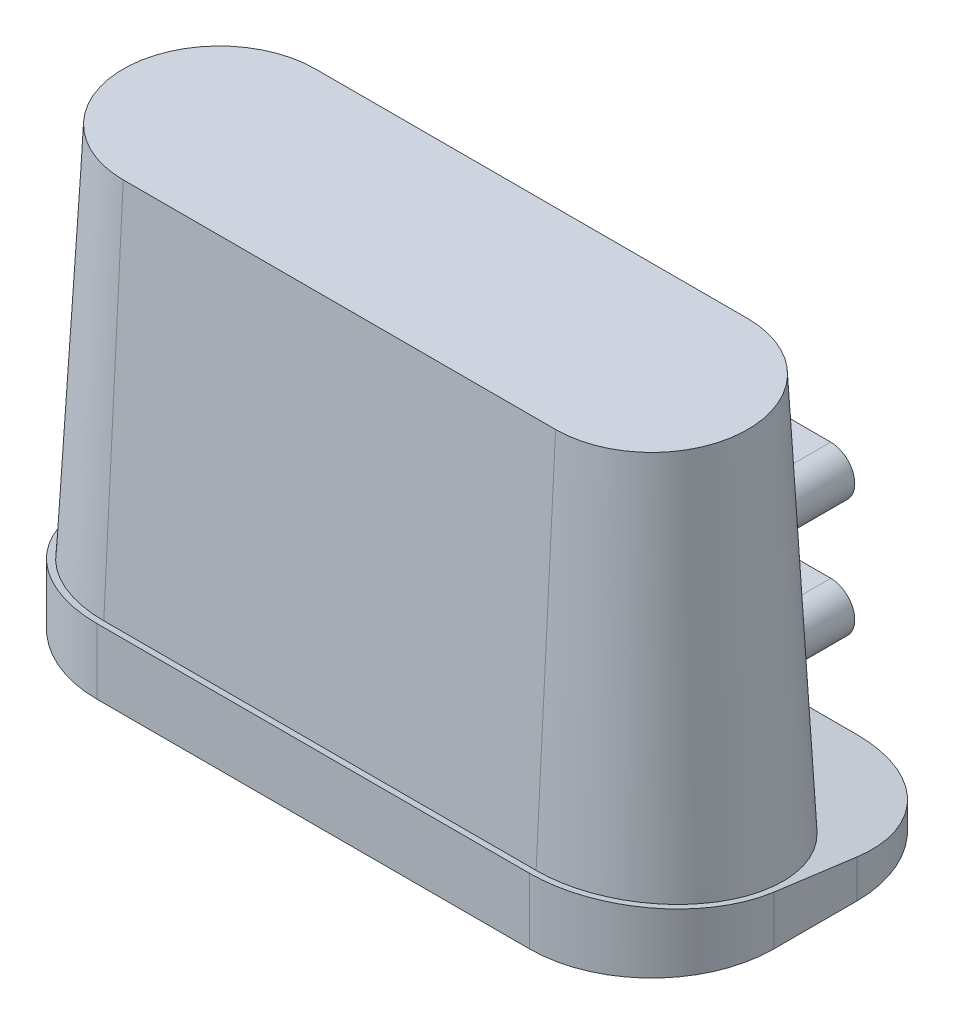
SolidWorks part; units mm, degrees
ref_plane "정면" through (0, 0, 0) normal (0, 0, 1) x (1, 0, 0)
ref_plane "윗면" through (0, 0, 0) normal (0, 1, 0) x (1, 0, 0)
ref_plane "우측면" through (0, 0, 0) normal (1, 0, 0) x (0, 0, -1)
sketch "스케치2" plane through (0, 0, 0) normal (0, 1, 0) x (1, 0, 0)
  line L1 (-77.5, -37.5) -> (77.5, -37.5)
  line L2 (-77.5, -37.5) -> (-77.5, 37.5)
  line L3 (-77.5, 37.5) -> (77.5, 37.5)
  line L4 (77.5, -37.5) -> (77.5, 37.5)
  line L5 (-77.5, -37.5) -> (77.5, 37.5) construction
  line L6 (-77.5, 37.5) -> (77.5, -37.5) construction
  point P0 (0, 0)
  dimension "D1" = 155
  dimension "D2" = 75
extrude "보스-돌출1" add sketch "스케치2" along normal blind 15
sketch "스케치3" plane through (77.5, 0, 0) normal (1, 0, 0) x (0, 0, -1)
  line L1 (37.5, 15) -> (37.5, 0) construction
  line L2 (37.5, 5) -> (-37.5, 15)
  line L8 (-37.5, 15) -> (37.5, 15)
  line L9 (37.5, 5) -> (37.5, 15)
extrude "컷-돌출1" cut sketch "스케치3" against normal through all
fillet "필렛1" radius 28 4 edges at (-77.5, 7.5, 37.5) (-77.5, 2.5, -37.5) (77.5, 2.5, -37.5) (77.5, 7.5, 37.5)
sketch "스케치4" plane through (0, 0, 0) normal (0, -1, 0) x (1, 0, 0)
  line L0 (-49.5, 9.5) -> (49.5, 9.5) construction
  line L1 (-49.5, 36.5) -> (49.5, 36.5)
  line L2 (-49.5, -17.5) -> (49.5, -17.5)
  line L3 (0, 37.5) -> (0, -37.5) construction
  line L4 (-49.5, 37.5) -> (49.5, 37.5) construction
  line L5 (49.5, -37.5) -> (-49.5, -37.5) construction
  line L6 (-77.5, -9.5) -> (-77.5, 9.5) construction
  arc A0 (-49.5, 36.5) -> (-49.5, -17.5) centre (-49.5, 9.5) ccw
  arc A1 (49.5, -17.5) -> (49.5, 36.5) centre (49.5, 9.5) ccw
  point P2 (0, 9.5)
  point P13 (0, 19.0079)
  point P14 (1.2515, 7.744)
  dimension "D2" = 27
  dimension "D4" = 28
  dimension "D1" = 99
  dimension "D3" = 1
extrude "보스-돌출2" add sketch "스케치4" against normal blind 100
chamfer "모따기1" distance 5 angle 87 4 edges at (0, 100, 36.5) (-76.5, 100, 9.5) (76.5, 100, 9.5) (0, 100, -17.5) first distance on face at (0, 100, 9.5)
sketch "스케치6" plane through (0, 0, 0) normal (0, 0, 1) x (1, 0, 0)
  line L0 (-51, 62) -> (51, 62) construction
  line L1 (-51, 67.5) -> (51, 67.5)
  line L2 (-51, 56.5) -> (51, 56.5)
  line L3 (-51, 35) -> (51, 35) construction
  line L4 (-51, 40.5) -> (51, 40.5)
  line L5 (-51, 29.5) -> (51, 29.5)
  line L6 (0, 0) -> (0, 100) construction
  line L7 (-49.5, 100) -> (49.5, 100) construction
  line L8 (-49.5, 5) -> (49.5, 5) construction
  arc A0 (-51, 67.5) -> (-51, 56.5) centre (-51, 62) ccw
  arc A1 (51, 56.5) -> (51, 67.5) centre (51, 62) ccw
  arc A2 (-51, 40.5) -> (-51, 29.5) centre (-51, 35) ccw
  arc A3 (51, 29.5) -> (51, 40.5) centre (51, 35) ccw
  point P2 (0, 62)
  point P7 (0, 35)
  point P19 (0, 78.238)
  point P20 (0, 41.1609)
  point P21 (-56.5, 62)
  point P22 (56.5, 62)
  point P23 (0, 41.6303)
  point P24 (0, 0)
  point P25 (0, 0)
  dimension "D1" = 5.5
  dimension "D2" = 113
  dimension "D3" = 16
  dimension "D4" = 24.5
extrude "보스-돌출3" add sketch "스케치6" against normal blind 30
sketch "스케치8" plane through (0, 0, -30) normal (0, 0, -1) x (-1, 0, 0)
  line L0 (-1.75, 89) -> (1.75, 89) construction
  line L1 (-1.75, 90) -> (1.75, 90)
  line L2 (-1.75, 88) -> (1.75, 88)
  line L3 (-49.5, 100) -> (49.5, 100) construction
  line L4 (0, 100) -> (0, 0) construction
  arc A0 (-1.75, 90) -> (-1.75, 88) centre (-1.75, 89) ccw
  arc A1 (1.75, 88) -> (1.75, 90) centre (1.75, 89) ccw
  point P2 (0, 89)
  point P12 (0, 89)
  dimension "D1" = 2
  dimension "D2" = 3.5
  dimension "D3" = 10
extrude "컷-돌출4" cut sketch "스케치8" against normal blind 0.2 from surface starting at face at (0, 83.75, -13.3516)
